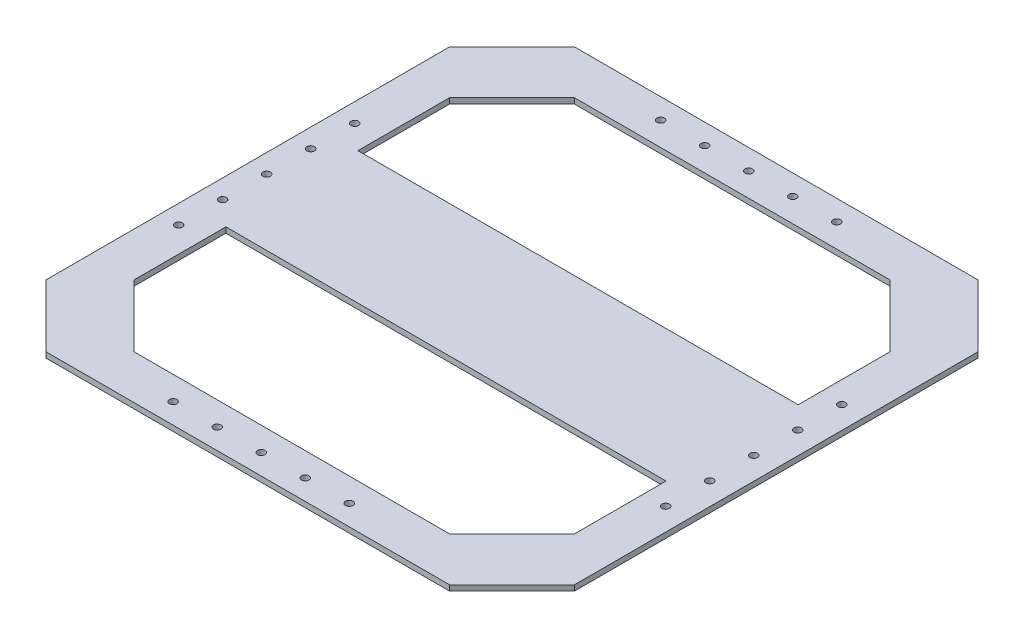
SolidWorks part; units mm, degrees
ref_plane "Front Plane" through (0, 0, 0) normal (0, 0, 1) x (1, 0, 0)
ref_plane "Top Plane" through (0, 0, 0) normal (0, 1, 0) x (1, 0, 0)
ref_plane "Right Plane" through (0, 0, 0) normal (1, 0, 0) x (0, 0, -1)
sketch "Sketch1" plane through (0, 0, 0) normal (0, 1, 0) x (1, 0, 0)
  line L0 (-148.336, 68.2596) -> (-112.415, 104.1807)
  line L1 (-112.415, 104.1807) -> (120.543, 104.1807)
  line L2 (-148.336, 68.2596) -> (-148.336, -164.6983)
  line L3 (156.464, 68.2596) -> (156.464, -164.6983)
  line L4 (156.464, 68.2596) -> (120.543, 104.1807)
  line L5 (4.064, 104.1807) -> (4.064, -200.6193) construction
  line L6 (-148.336, -48.2193) -> (156.464, -48.2193) construction
  line L7 (156.464, -164.6983) -> (120.543, -200.6193)
  line L8 (-112.415, -200.6193) -> (120.543, -200.6193)
  line L9 (-148.336, -164.6983) -> (-112.415, -200.6193)
  point P9 (4.064, -48.2193)
  point P11 (4.064, -48.2193)
  dimension "D3" = 50.8
  dimension "D4" = 135
extrude "Boss-Extrude1" add sketch "Sketch1" along normal blind 3.175
sketch "Sketch2" plane through (0, 3.175, 0) normal (0, 1, 0) x (1, 0, 0)
  line L0 (-148.336, -48.2193) -> (199.0625, -48.2193) construction
  line L1 (-148.336, 68.2596) -> (-148.336, -164.6983) construction
  line L2 (-87.015, 78.7807) -> (95.143, 78.7807)
  line L4 (82.443, -10.1193) -> (-74.315, -10.1193)
  line L6 (-112.415, 104.1807) -> (-87.015, 78.7807) construction
  line L7 (120.543, 104.1807) -> (95.143, 78.7807) construction
  line L8 (120.543, 104.1807) -> (-112.415, 104.1807) construction
  line L9 (-74.315, -10.1193) -> (-122.936, -10.1193)
  line L10 (-122.936, -10.1193) -> (-122.936, 42.8596)
  line L11 (-122.936, 42.8596) -> (-87.015, 78.7807)
  line L12 (82.443, -10.1193) -> (131.064, -10.1193)
  line L13 (131.064, -10.1193) -> (131.064, 42.8596)
  line L14 (131.064, 42.8596) -> (95.143, 78.7807)
  line L16 (131.064, -139.2983) -> (95.143, -175.2193)
  line L17 (131.064, -86.3193) -> (131.064, -139.2983)
  line L18 (82.443, -86.3193) -> (131.064, -86.3193)
  line L19 (-122.936, -139.2983) -> (-87.015, -175.2193)
  line L20 (-122.936, -86.3193) -> (-122.936, -139.2983)
  line L21 (-74.315, -86.3193) -> (-122.936, -86.3193)
  line L23 (82.443, -86.3193) -> (-74.315, -86.3193)
  line L25 (-87.015, -175.2193) -> (95.143, -175.2193)
  dimension "D1" = 135
  dimension "D2" = 135
  dimension "D3" = 25.4
  dimension "D4" = 90
  dimension "D5" = 90
  dimension "D6" = 50.8
  dimension "D7" = 50.8
  dimension "D8" = 38.1
extrude "Cut-Extrude1" cut sketch "Sketch2" against normal through all
sketch "Sketch4" plane through (0, 3.175, 0) normal (0, 1, 0) x (1, 0, 0)
  line L0 (-148.336, -48.2193) -> (171.6111, -48.2193) construction
  line L1 (-148.336, 68.2596) -> (-148.336, -164.6983) construction
  circle A0 centre (0, 92.4278) radius 2.159
  circle A1 centre (-50.8, 92.4278) radius 2.159
  circle A2 centre (50.8, 92.4278) radius 2.159
  circle A3 centre (-25.4, 92.4278) radius 2.159
  circle A4 centre (25.4, 92.4278) radius 2.159
  circle A5 centre (-137.4911, -48.2193) radius 2.159
  circle A6 centre (-137.4911, -22.8193) radius 2.159
  circle A7 centre (-137.4911, 2.5807) radius 2.159
  circle A8 centre (143.542, -48.2193) radius 2.159
  circle A9 centre (143.542, -22.8193) radius 2.159
  circle A10 centre (143.542, 2.5807) radius 2.159
  circle A11 centre (143.542, -99.0193) radius 2.159
  circle A12 centre (143.542, -73.6193) radius 2.159
  circle A13 centre (-137.4911, -99.0193) radius 2.159
  circle A14 centre (-137.4911, -73.6193) radius 2.159
  circle A15 centre (25.4, -188.8665) radius 2.159
  circle A16 centre (-25.4, -188.8665) radius 2.159
  circle A17 centre (50.8, -188.8665) radius 2.159
  circle A18 centre (-50.8, -188.8665) radius 2.159
  circle A19 centre (0, -188.8665) radius 2.159
  point P26 (0, 0)
  dimension "D1" = 4.318
  dimension "D2" = 4.318
  dimension "D3" = 4.318
  dimension "D4" = 4.318
  dimension "D5" = 4.318
  dimension "D6" = 4.318
  dimension "D7" = 4.318
  dimension "D8" = 4.318
  dimension "D9" = 4.318
  dimension "D10" = 4.318
  dimension "D11" = 4.318
  dimension "D12" = 25.4
  dimension "D13" = 25.4
  dimension "D14" = 25.4
  dimension "D15" = 25.4
  dimension "D16" = 25.4
  dimension "D17" = 25.4
  dimension "D18" = 25.4
  dimension "D19" = 25.4
extrude "Cut-Extrude2" cut sketch "Sketch4" against normal through all
sketch "Sketch5" plane through (0, 3.175, 0) normal (0, 1, 0) x (1, 0, 0)
  line L0 (-104.9755, 60.8201) -> (-94.4545, 50.2991) construction
  line L1 (-112.415, 32.3386) -> (-76.494, 68.2596)
  line L2 (-87.015, 78.7807) -> (-122.936, 42.8596) construction
  line L3 (-148.336, 11.1385) -> (-122.936, 11.1385)
  line L4 (-122.936, 42.8596) -> (-122.936, -10.1193) construction
  line L5 (95.143, 78.7807) -> (-87.015, 78.7807) construction
  line L6 (-54.4523, 78.7807) -> (-54.4523, 104.1807)
  line L7 (120.543, 104.1807) -> (-112.415, 104.1807) construction
  line L8 (-54.4523, 104.1807) -> (-112.415, 104.1807)
  line L9 (-112.415, 104.1807) -> (-148.336, 68.2596)
  line L10 (-148.336, 68.2596) -> (-148.336, 11.1385)
  line L11 (-148.336, 68.2596) -> (-148.336, -164.6983) construction
  line L16 (4.064, 104.1807) -> (4.064, -253.7434) construction
  line L17 (156.464, -48.2193) -> (-206.1524, -48.2193) construction
  line L19 (-148.336, 11.1385) -> (-148.336, 68.2596)
  line L23 (156.464, -164.6983) -> (156.464, 68.2596) construction
  line L24 (113.1035, 60.8201) -> (102.5825, 50.2991) construction
  line L25 (84.622, 68.2596) -> (84.622, 72.4307)
  line L26 (131.064, 25.9886) -> (131.064, 10.297)
  line L27 (131.064, 10.297) -> (156.464, 10.297)
  line L28 (156.464, 10.297) -> (156.464, 68.2596)
  line L29 (120.543, 32.3386) -> (124.714, 32.3386)
  line L30 (84.622, 68.2596) -> (84.622, 72.4307)
  line L31 (131.064, 11.1385) -> (131.064, 25.9886)
  line L32 (156.464, 11.1385) -> (131.064, 11.1385)
  line L33 (156.464, 68.2596) -> (156.464, 11.1385)
  line L34 (120.543, 104.1807) -> (156.464, 68.2596)
  line L35 (62.5803, 104.1807) -> (120.543, 104.1807)
  line L36 (62.5803, 78.7807) -> (62.5803, 104.1807)
  line L37 (78.272, 78.7807) -> (62.5803, 78.7807)
  line L38 (120.543, 32.3386) -> (124.714, 32.3386)
  line L39 (120.543, 32.3386) -> (84.622, 68.2596)
  line L40 (113.1035, -157.2588) -> (102.5825, -146.7378) construction
  line L41 (-104.9755, -157.2588) -> (-94.4545, -146.7378) construction
  line L42 (120.543, -128.7773) -> (84.622, -164.6983)
  line L43 (120.543, -128.7773) -> (124.714, -128.7773)
  line L44 (78.272, -175.2193) -> (62.5803, -175.2193)
  line L45 (62.5803, -175.2193) -> (62.5803, -200.6193)
  line L46 (62.5803, -200.6193) -> (120.543, -200.6193)
  line L47 (120.543, -200.6193) -> (156.464, -164.6983)
  line L48 (156.464, -164.6983) -> (156.464, -107.5772)
  line L49 (156.464, -107.5772) -> (131.064, -107.5772)
  line L50 (131.064, -107.5772) -> (131.064, -122.4273)
  line L51 (84.622, -164.6983) -> (84.622, -168.8693)
  line L52 (120.543, -128.7773) -> (124.714, -128.7773)
  line L53 (156.464, -106.7357) -> (156.464, -164.6983)
  line L54 (131.064, -106.7357) -> (156.464, -106.7357)
  line L55 (131.064, -122.4273) -> (131.064, -106.7357)
  line L56 (84.622, -164.6983) -> (84.622, -168.8693)
  line L57 (-76.494, -164.6983) -> (-76.494, -168.8693)
  line L58 (-122.936, -122.4273) -> (-122.936, -106.7357)
  line L59 (-122.936, -106.7357) -> (-148.336, -106.7357)
  line L60 (-148.336, -106.7357) -> (-148.336, -164.6983)
  line L61 (-112.415, -128.7773) -> (-116.586, -128.7773)
  line L62 (-76.494, -164.6983) -> (-76.494, -168.8693)
  line L63 (-122.936, -107.5772) -> (-122.936, -122.4273)
  line L64 (-148.336, -107.5772) -> (-122.936, -107.5772)
  line L65 (-148.336, -164.6983) -> (-148.336, -107.5772)
  line L66 (-112.415, -200.6193) -> (-148.336, -164.6983)
  line L67 (-54.4523, -200.6193) -> (-112.415, -200.6193)
  line L68 (-54.4523, -175.2193) -> (-54.4523, -200.6193)
  line L69 (-70.144, -175.2193) -> (-54.4523, -175.2193)
  line L70 (-112.415, -128.7773) -> (-116.586, -128.7773)
  line L71 (-112.415, -128.7773) -> (-76.494, -164.6983)
  arc A4 (131.064, 25.9886) -> (124.714, 32.3386) centre (124.714, 25.9886) ccw
  arc A5 (78.272, 78.7807) -> (84.622, 72.4307) centre (78.272, 72.4307) cw
  arc A6 (131.064, 25.9886) -> (124.714, 32.3386) centre (124.714, 25.9886) ccw
  arc A7 (78.272, 78.7807) -> (84.622, 72.4307) centre (78.272, 72.4307) cw
  arc A8 (78.272, -175.2193) -> (84.622, -168.8693) centre (78.272, -168.8693) ccw
  arc A9 (131.064, -122.4273) -> (124.714, -128.7773) centre (124.714, -122.4273) cw
  arc A10 (78.272, -175.2193) -> (84.622, -168.8693) centre (78.272, -168.8693) ccw
  arc A11 (131.064, -122.4273) -> (124.714, -128.7773) centre (124.714, -122.4273) cw
  arc A12 (-122.936, -122.4273) -> (-116.586, -128.7773) centre (-116.586, -122.4273) ccw
  arc A13 (-70.144, -175.2193) -> (-76.494, -168.8693) centre (-70.144, -168.8693) cw
  arc A14 (-122.936, -122.4273) -> (-116.586, -128.7773) centre (-116.586, -122.4273) ccw
  arc A15 (-70.144, -175.2193) -> (-76.494, -168.8693) centre (-70.144, -168.8693) cw
  dimension "D1" = 50.8
  dimension "D2" = 90
  dimension "D4" = 50.8
extrude "Boss-Extrude2" add sketch "Sketch5" against normal blind 3.175 rebuild error yes
